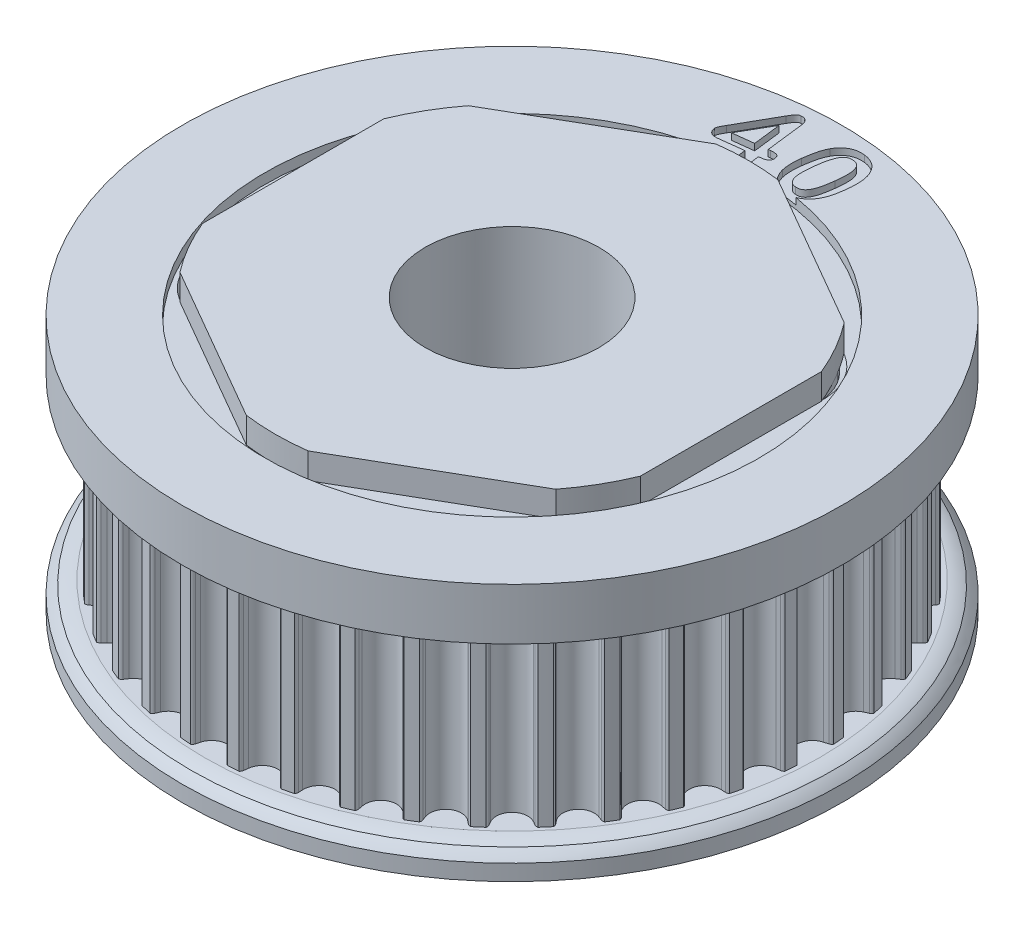
SolidWorks part; units mm, degrees
other "DetailItem2"
material "Markforged"
ref_plane "Front Plane" through (0, 0, 0) normal (0, 0, 1) x (1, 0, 0)
ref_plane "Top Plane" through (0, 0, 0) normal (0, 1, 0) x (1, 0, 0)
ref_plane "Right Plane" through (0, 0, 0) normal (1, 0, 0) x (0, 0, -1)
ref_axis "Centerline" through (0, 8.7312, 0) along (0, -1, 0)
sketch "Sketch1" plane through (0, 0, 0) normal (0, 1, 0) x (1, 0, 0)
  circle A0 centre (0, 0) radius 18.7176
  dimension "OuterDiameter" = 37.4352
extrude "ToothOD" add sketch "Sketch1" along normal mid plane 12.3825
sketch "Sketch2" plane through (0, 0, 0) normal (0, 1, 0) x (1, 0, 0)
  line L0 (0, 17.5492) -> (50000, 17.5492) construction
  line L1 (0, 18.7176) -> (50000, 18.7176) construction
  line L2 (0, 0) -> (0, 50000) construction
  arc A0 (-0.937, 18.2677) -> (0, 17.5492) centre (0, 18.5195) ccw
  arc A1 (-1.1278, 18.6836) -> (1.1278, 18.6836) centre (0, 0) cw
  circle A2 centre (0, 0) radius 18.7176 construction
  arc A3 (-0.937, 18.2677) -> (-1.0078, 18.5195) centre (-11.9754, 15.3012) ccw
  arc A4 (-1.0078, 18.5195) -> (-1.1278, 18.6836) centre (-1.2954, 18.4351) ccw
  circle A5 centre (0, 0) radius 18.7176 construction
  arc A6 (0.937, 18.2677) -> (1.0078, 18.5195) centre (11.9754, 15.3012) cw
  arc A7 (1.0078, 18.5195) -> (1.1278, 18.6836) centre (1.2954, 18.4351) cw
  arc A8 (0, 17.5492) -> (0.937, 18.2677) centre (0, 18.5195) ccw
  dimension "D1" = 1.9406
  dimension "D3" = 22.86
  dimension "D4" = 0.5994
  dimension "D2" = 1.1684
  dimension "D5" = 1.2954
extrude "ToothProfile" cut sketch "Sketch2" against normal through all both and the other way through all
pattern_circular "ToothPattern" count 40 over 360 about axis through (0, 6.1913, 0) along (0, -1, 0) of "ToothProfile"
sketch "Sketch4" plane through (0, 0, 0) normal (0, 0, 1) x (1, 0, 0)
  line L0 (0, -6.1913) -> (18.9716, -6.1913)
  line L1 (0, -7.9375) -> (20.32, -7.9375)
  line L2 (0, -7.9375) -> (0, -6.1913)
  line L3 (20.32, -7.9375) -> (20.32, -6.9532)
  line L4 (0, 0) -> (50000, 0) construction
  line L5 (20.32, 7.9375) -> (20.32, 6.9532)
  line L6 (0, 7.9375) -> (0, 6.1913)
  line L7 (0, 7.9375) -> (20.32, 7.9375)
  line L8 (0, 6.1913) -> (18.9716, 6.1913) construction
  line L9 (0, 6.1913) -> (0, 3.9688)
  line L10 (0, 3.9688) -> (18.9716, 3.9688)
  line L11 (18.9716, 3.9688) -> (20.32, 4.7473)
  line L12 (20.32, 4.7473) -> (20.32, 6.9532)
  line L13 (18.9716, 3.9688) -> (18.9716, 6.1913) construction
  arc A0 (18.9716, -6.1913) -> (19.812, -6.4452) centre (18.6641, -8.7261) cw
  arc A2 (19.812, -6.4452) -> (20.32, -6.9532) centre (17.815, -8.9503) cw
  arc A3 (19.812, 6.4452) -> (20.32, 6.9532) centre (17.815, 8.9503) ccw construction
  arc A4 (18.9716, 6.1913) -> (19.812, 6.4452) centre (18.6641, 8.7261) ccw construction
  dimension "D5" = 2.5534
  dimension "D6" = 3.2036
  dimension "FlangeID" = 18.9716
  dimension "D1" = 1.7463
  dimension "D2" = 0.9843
  dimension "D3" = 6.1913
  dimension "D4" = 15.875
  dimension "D7" = 0.762
  dimension "D8" = 0.508
  dimension "D10" = 0.508
  dimension "D9" = 20.32
  dimension "D11" = 10.16
  dimension "D12" = 30
revolve "Flange" add sketch "Sketch4" angle 360 about axis through (0, 8.7312, 0) along (0, -1, 0)
sketch "Sketch7" plane through (0, 0, 0) normal (0, -1, 0) x (1, 0, 0)
  circle A0 centre (0, 0) radius 5.3581
  dimension "D1" = 10.7163
extrude "Bore" cut sketch "Sketch7" against normal through all both and the other way through all
sketch "Sketch9" plane through (0, 7.9375, 0) normal (0, 1, 0) x (1, 0, 0)
  arc A0 (-10.7763, -10.7763) -> (10.7763, -10.7763) centre (0, 0) cw construction
  text T0 "40" font "Arial Rounded MT Bold" height 4.572
  point P3 (0, 15.24)
  dimension "D1" = 15.24
  dimension "D2" = 270
extrude "Large Tooth Count" cut sketch "Sketch9" against normal blind 0.4 and the other way through all
sketch "Sketch11" plane through (0, 7.9375, 0) normal (0, 1, 0) x (1, 0, 0)
  arc A0 (-4.8314, -4.8314) -> (4.8314, -4.8314) centre (0, 0) cw construction
  text T0 "<b>40</b>" font "Arial Rounded MT Bold" height 2.286
  point P6 (0, 6.8326)
  dimension "D4" = 6.8326
  dimension "D3" = 270
extrude "Small Tooth Count" [suppressed] cut sketch "Sketch11" against normal blind 0.4 and the other way through all
sketch "Sketch14" plane through (0, 0, 0) normal (0, 0, 1) x (1, 0, 0)
  line L0 (20.32, 7.9375) -> (-20.32, 7.9375) construction
  line L1 (0, 7.9375) -> (15.24, 7.9375)
  line L2 (0, 7.9375) -> (0, 7.3025)
  line L3 (0, 7.3025) -> (15.24, 7.3025)
  line L4 (15.24, 7.9375) -> (15.24, 7.3025)
  line L5 (0, 7.9375) -> (15.24, 7.3025) construction
  line L6 (0, 7.3025) -> (15.24, 7.9375) construction
  line L7 (-20.32, -7.9375) -> (20.32, -7.9375) construction
  line L8 (0, -7.9375) -> (15.24, -7.9375)
  line L9 (0, -7.9375) -> (0, -2.2225)
  line L10 (0, -2.2225) -> (15.24, -2.2225)
  line L11 (15.24, -7.9375) -> (15.24, -2.2225)
  line L12 (0, -7.9375) -> (15.24, -2.2225) construction
  line L13 (0, -2.2225) -> (15.24, -7.9375) construction
  line L14 (0, 0) -> (0, 50000) construction
  point P4 (7.62, 7.62)
  point P11 (7.62, -5.08)
  dimension "D1" = 9.525
  dimension "D2" = 15.24
  dimension "D3" = 10.16
revolve "Cut-Revolve1" cut sketch "Sketch14" angle 360 about L14
sketch "Sketch15" plane through (0, -7.9375, 0) normal (0, -1, 0) x (1, 0, 0)
  line L0 (0, 0) -> (0, 11.43) construction
  line L1 (-3.175, 0) -> (-3.175, 11.43)
  line L2 (3.175, 0) -> (3.175, 11.43)
  arc A0 (-3.175, 0) -> (3.175, 0) centre (0, 0) ccw
  arc A1 (3.175, 11.43) -> (-3.175, 11.43) centre (0, 11.43) ccw
  point P3 (0, 5.715)
  dimension "D1" = 3.175
  dimension "D2" = 11.43
extrude "Cut-Extrude1" cut sketch "Sketch15" against normal through all
pattern_circular "CirPattern1" count 6 over 360 about axis through (0, 7.9375, 0) along (0, -1, 0) of "Cut-Extrude1"
fillet "Fillet1" radius 3.175 6 edges at (-6.35, 2.54, 0) (-3.175, 2.54, -5.4993) (3.175, 2.54, -5.4993) (6.35, 2.54, 0) (-3.175, 2.54, 5.4993) (3.175, 2.54, 5.4993)
sketch "Sketch17" plane through (0, -2.2225, 0) normal (0, -1, 0) x (1, 0, 0)
  line L14 (3.175, 10.9985) -> (3.175, 11.43)
  line L16 (8.3112, 8.4646) -> (7.9375, 8.2489)
  line L18 (11.1125, 2.7496) -> (11.4862, 2.9654)
  line L20 (11.4862, -2.9654) -> (11.1125, -2.7496)
  line L22 (7.9375, -8.2489) -> (8.3112, -8.4646)
  line L24 (3.175, -11.43) -> (3.175, -10.9985)
  line L26 (-3.175, -10.9985) -> (-3.175, -11.43)
  line L28 (-8.3112, -8.4646) -> (-7.9375, -8.2489)
  line L30 (-11.1125, -2.7496) -> (-11.4862, -2.9654)
  line L32 (-11.4862, 2.9654) -> (-11.1125, 2.7496)
  line L34 (-7.9375, 8.2489) -> (-8.3112, 8.4646)
  line L37 (-3.175, 11.43) -> (-3.175, 10.9985)
  line L50 (3.175, 10.9985) -> (3.175, 11.43)
  line L51 (8.3112, 8.4646) -> (7.9375, 8.2489)
  line L52 (11.1125, 2.7496) -> (11.4862, 2.9654)
  line L53 (11.4862, -2.9654) -> (11.1125, -2.7496)
  line L54 (7.9375, -8.2489) -> (8.3112, -8.4646)
  line L55 (3.175, -11.43) -> (3.175, -10.9985)
  line L56 (-3.175, -10.9985) -> (-3.175, -11.43)
  line L57 (-8.3112, -8.4646) -> (-7.9375, -8.2489)
  line L58 (-11.1125, -2.7496) -> (-11.4862, -2.9654)
  line L59 (-11.4862, 2.9654) -> (-11.1125, 2.7496)
  line L60 (-7.9375, 8.2489) -> (-8.3112, 8.4646)
  line L61 (-3.175, 11.43) -> (-3.175, 10.9985)
  circle A1 centre (0, 0) radius 5.3581 construction
  circle A8 centre (0, 0) radius 5.3581
  arc A47 (3.175, 10.9985) -> (7.9375, 8.2489) centre (6.35, 10.9985) ccw
  arc A48 (11.4862, 2.9654) -> (8.3112, 8.4646) centre (9.8987, 5.715) ccw
  arc A49 (11.1125, 2.7496) -> (11.1125, -2.7496) centre (12.7, 0) ccw
  arc A50 (8.3112, -8.4646) -> (11.4862, -2.9654) centre (9.8987, -5.715) ccw
  arc A51 (7.9375, -8.2489) -> (3.175, -10.9985) centre (6.35, -10.9985) ccw
  arc A52 (-3.175, -11.43) -> (3.175, -11.43) centre (0, -11.43) ccw
  arc A53 (-3.175, -10.9985) -> (-7.9375, -8.2489) centre (-6.35, -10.9985) ccw
  arc A54 (-11.4862, -2.9654) -> (-8.3112, -8.4646) centre (-9.8987, -5.715) ccw
  arc A55 (-11.1125, -2.7496) -> (-11.1125, 2.7496) centre (-12.7, 0) ccw
  arc A56 (-8.3112, 8.4646) -> (-11.4862, 2.9654) centre (-9.8987, 5.715) ccw
  arc A57 (-7.9375, 8.2489) -> (-3.175, 10.9985) centre (-6.35, 10.9985) ccw
  arc A70 (3.175, 11.43) -> (-3.175, 11.43) centre (0, 11.43) ccw
  arc A71 (3.175, 10.9985) -> (7.9375, 8.2489) centre (6.35, 10.9985) ccw
  arc A72 (11.4862, 2.9654) -> (8.3112, 8.4646) centre (9.8987, 5.715) ccw
  arc A73 (11.1125, 2.7496) -> (11.1125, -2.7496) centre (12.7, 0) ccw
  arc A74 (8.3112, -8.4646) -> (11.4862, -2.9654) centre (9.8987, -5.715) ccw
  arc A75 (7.9375, -8.2489) -> (3.175, -10.9985) centre (6.35, -10.9985) ccw
  arc A76 (-3.175, -11.43) -> (3.175, -11.43) centre (0, -11.43) ccw
  arc A77 (-3.175, -10.9985) -> (-7.9375, -8.2489) centre (-6.35, -10.9985) ccw
  arc A78 (-11.4862, -2.9654) -> (-8.3112, -8.4646) centre (-9.8987, -5.715) ccw
  arc A79 (-11.1125, -2.7496) -> (-11.1125, 2.7496) centre (-12.7, 0) ccw
  arc A80 (-8.3112, 8.4646) -> (-11.4862, 2.9654) centre (-9.8987, 5.715) ccw
  arc A81 (-7.9375, 8.2489) -> (-3.175, 10.9985) centre (-6.35, 10.9985) ccw
  arc A82 (3.175, 11.43) -> (-3.175, 11.43) centre (0, 11.43) ccw
  dimension "D1" = 0
extrude "Boss-Extrude1" add sketch "Sketch17" against normal up to surface (9.525 mm away) separate body up to face at (0, 7.3025, 0)
sketch "Sketch21" plane through (0, -2.2225, 0) normal (0, -1, 0) x (1, 0, 0)
  circle A0 centre (0, 0) radius 7.9375
  dimension "D1" = 15.875
extrude "Cut-Extrude4" cut sketch "Sketch21" against normal blind 2.286
chamfer "Chamfer1" distance 2.54 angle 45 1 edges at (0, -7.9375, -15.24)
chamfer "Chamfer2" distance 0.635 angle 45 1 edges at (0, -2.2225, -15.24)
sketch "Sketch22" plane through (0, 7.3025, 0) normal (0, 1, 0) x (1, 0, 0)
  circle A0 centre (0, 0) radius 5.3581
  circle A1 centre (0, 0) radius 14.605
  arc A2 (8.3112, -8.4646) -> (11.4862, -2.9654) centre (9.8987, -5.715) ccw construction
  circle A3 centre (0, 0) radius 5.3581 construction
extrude "Boss-Extrude2" add sketch "Sketch22" along normal blind 1.5875 separate body
combine bodies "Combine1" operation type add bodies to combine 118 117
sketch "Sketch23" plane through (0, 7.3025, 0) normal (0, 1, 0) x (1, 0, 0)
  line L0 (7.9058, -8.3039) -> (8.2794, -8.5196)
  line L1 (11.5179, -2.9104) -> (11.1442, -2.6946)
  line L2 (11.1442, 2.6946) -> (11.5179, 2.9104)
  line L3 (8.2794, 8.5196) -> (7.9057, 8.3039)
  line L4 (3.2385, 10.9985) -> (3.2385, 11.43)
  line L5 (-3.2385, 11.43) -> (-3.2385, 10.9985)
  line L6 (-7.9058, 8.3039) -> (-8.2794, 8.5196)
  line L7 (-11.5179, 2.9104) -> (-11.1442, 2.6946)
  line L8 (-11.1442, -2.6946) -> (-11.5179, -2.9104)
  line L9 (-8.2794, -8.5196) -> (-7.9057, -8.3039)
  line L10 (-3.2385, -10.9985) -> (-3.2385, -11.43)
  line L11 (3.2385, -11.43) -> (3.2385, -10.9985)
  line L12 (7.9375, -8.2489) -> (8.3112, -8.4646)
  line L13 (3.175, -11.43) -> (3.175, -10.9985)
  line L14 (-3.175, -10.9985) -> (-3.175, -11.43)
  line L15 (-8.3112, -8.4646) -> (-7.9375, -8.2489)
  line L16 (-11.1125, -2.7496) -> (-11.4862, -2.9654)
  line L17 (-11.4862, 2.9654) -> (-11.1125, 2.7496)
  line L18 (-7.9375, 8.2489) -> (-8.3112, 8.4646)
  line L19 (-3.175, 11.43) -> (-3.175, 10.9985)
  line L20 (3.175, 10.9985) -> (3.175, 11.43)
  line L21 (8.3112, 8.4646) -> (7.9375, 8.2489)
  line L22 (11.1125, 2.7496) -> (11.4862, 2.9654)
  line L23 (11.4862, -2.9654) -> (11.1125, -2.7496)
  line L24 (7.9375, -8.2489) -> (8.3112, -8.4646)
  line L25 (3.175, -11.43) -> (3.175, -10.9985)
  line L26 (-3.175, -10.9985) -> (-3.175, -11.43)
  line L27 (-8.3112, -8.4646) -> (-7.9375, -8.2489)
  line L28 (-11.1125, -2.7496) -> (-11.4862, -2.9654)
  line L29 (-11.4862, 2.9654) -> (-11.1125, 2.7496)
  line L30 (-7.9375, 8.2489) -> (-8.3112, 8.4646)
  line L31 (-3.175, 11.43) -> (-3.175, 10.9985)
  line L32 (3.175, 10.9985) -> (3.175, 11.43)
  line L33 (8.3112, 8.4646) -> (7.9375, 8.2489)
  line L34 (11.1125, 2.7496) -> (11.4862, 2.9654)
  line L35 (11.4862, -2.9654) -> (11.1125, -2.7496)
  arc A0 (8.2794, -8.5196) -> (11.5179, -2.9104) centre (9.8987, -5.715) ccw
  arc A1 (11.1442, 2.6946) -> (11.1442, -2.6946) centre (12.7, 0) ccw
  arc A2 (11.5179, 2.9104) -> (8.2794, 8.5196) centre (9.8987, 5.715) ccw
  arc A3 (3.2385, 10.9985) -> (7.9057, 8.3039) centre (6.35, 10.9985) ccw
  arc A4 (3.2385, 11.43) -> (-3.2385, 11.43) centre (0, 11.43) ccw
  arc A5 (-7.9058, 8.3039) -> (-3.2385, 10.9985) centre (-6.35, 10.9985) ccw
  arc A6 (-8.2794, 8.5196) -> (-11.5179, 2.9104) centre (-9.8987, 5.715) ccw
  arc A7 (-11.1442, -2.6946) -> (-11.1442, 2.6946) centre (-12.7, 0) ccw
  arc A8 (-11.5179, -2.9104) -> (-8.2794, -8.5196) centre (-9.8987, -5.715) ccw
  arc A9 (-3.2385, -10.9985) -> (-7.9057, -8.3039) centre (-6.35, -10.9985) ccw
  arc A10 (-3.2385, -11.43) -> (3.2385, -11.43) centre (0, -11.43) ccw
  arc A11 (7.9058, -8.3039) -> (3.2385, -10.9985) centre (6.35, -10.9985) ccw
  arc A12 (7.9375, -8.2489) -> (3.175, -10.9985) centre (6.35, -10.9985) ccw
  arc A13 (-3.175, -11.43) -> (3.175, -11.43) centre (0, -11.43) ccw
  arc A14 (-3.175, -10.9985) -> (-7.9375, -8.2489) centre (-6.35, -10.9985) ccw
  arc A15 (-11.4862, -2.9654) -> (-8.3112, -8.4646) centre (-9.8987, -5.715) ccw
  arc A16 (-11.1125, -2.7496) -> (-11.1125, 2.7496) centre (-12.7, 0) ccw
  arc A17 (-8.3112, 8.4646) -> (-11.4862, 2.9654) centre (-9.8987, 5.715) ccw
  arc A18 (-7.9375, 8.2489) -> (-3.175, 10.9985) centre (-6.35, 10.9985) ccw
  arc A19 (3.175, 11.43) -> (-3.175, 11.43) centre (0, 11.43) ccw
  arc A20 (3.175, 10.9985) -> (7.9375, 8.2489) centre (6.35, 10.9985) ccw
  arc A21 (11.4862, 2.9654) -> (8.3112, 8.4646) centre (9.8987, 5.715) ccw
  arc A22 (11.1125, 2.7496) -> (11.1125, -2.7496) centre (12.7, 0) ccw
  arc A23 (8.3112, -8.4646) -> (11.4862, -2.9654) centre (9.8987, -5.715) ccw
  arc A24 (7.9375, -8.2489) -> (3.175, -10.9985) centre (6.35, -10.9985) ccw
  arc A25 (-3.175, -11.43) -> (3.175, -11.43) centre (0, -11.43) ccw
  arc A26 (-3.175, -10.9985) -> (-7.9375, -8.2489) centre (-6.35, -10.9985) ccw
  arc A27 (-11.4862, -2.9654) -> (-8.3112, -8.4646) centre (-9.8987, -5.715) ccw
  arc A28 (-11.1125, -2.7496) -> (-11.1125, 2.7496) centre (-12.7, 0) ccw
  arc A29 (-8.3112, 8.4646) -> (-11.4862, 2.9654) centre (-9.8987, 5.715) ccw
  arc A30 (-7.9375, 8.2489) -> (-3.175, 10.9985) centre (-6.35, 10.9985) ccw
  arc A31 (3.175, 11.43) -> (-3.175, 11.43) centre (0, 11.43) ccw
  arc A32 (3.175, 10.9985) -> (7.9375, 8.2489) centre (6.35, 10.9985) ccw
  arc A33 (11.4862, 2.9654) -> (8.3112, 8.4646) centre (9.8987, 5.715) ccw
  arc A34 (11.1125, 2.7496) -> (11.1125, -2.7496) centre (12.7, 0) ccw
  arc A35 (8.3112, -8.4646) -> (11.4862, -2.9654) centre (9.8987, -5.715) ccw
  dimension "D1" = 0
  dimension "D2" = 0.0635
extrude "Cut-Extrude5" cut sketch "Sketch23" against normal through all
chamfer "Chamfer3" distance 0.3175 angle 45 54 edges at (-4.7942, 7.3025, 8.3039) (-3.2385, 7.3025, 11.2143) (-8.0926, 7.3025, 8.4118) (0, 7.3025, 14.6685) (-12.7033, 7.3025, 7.3342) (3.2385, 7.3025, 11.2143) (-11.3311, 7.3025, 2.8025) (4.7943, 7.3025, 8.3039) (-9.5885, 7.3025, 0) (8.0926, 7.3025, 8.4118) (-11.3311, 7.3025, -2.8025) (12.7033, 7.3025, 7.3343) (-12.7033, 7.3025, -7.3343) (11.3311, 7.3025, 2.8025) (-8.0926, 7.3025, -8.4118) (9.5885, 7.3025, 0) (-4.7943, 7.3025, -8.3039) (11.3311, 7.3025, -2.8025) (-3.2385, 7.3025, -11.2143) (12.7033, 7.3025, -7.3342) (0, 7.3025, -14.6685) (8.0926, 7.3025, -8.4118) (3.2385, 7.3025, -11.2143) (4.7942, 7.3025, -8.3039) (-10.3811, -2.2225, 8.9174) (-2.5321, -2.2225, 13.449) (-8.0926, -2.2225, 8.4118) (-3.2385, -2.2225, 11.2143) (-4.7942, -2.2225, 8.3039) (2.5321, -2.2225, 13.449) (10.3811, -2.2225, 8.9174) (3.2385, -2.2225, 11.2143) (8.0926, -2.2225, 8.4118) (4.7943, -2.2225, 8.3039) (12.9132, -2.2225, 4.5316) (12.9132, -2.2225, -4.5316) (11.3311, -2.2225, 2.8025) (11.3311, -2.2225, -2.8025) (9.5885, -2.2225, 0) (10.3811, -2.2225, -8.9174) (2.5321, -2.2225, -13.449) (8.0926, -2.2225, -8.4118) (3.2385, -2.2225, -11.2143) (4.7942, -2.2225, -8.3039) (-2.5321, -2.2225, -13.449) (-10.3811, -2.2225, -8.9174) (-3.2385, -2.2225, -11.2143) (-8.0926, -2.2225, -8.4118) (-4.7943, -2.2225, -8.3039) (-12.9132, -2.2225, -4.5316) (-12.9132, -2.2225, 4.5316) (-11.3311, -2.2225, -2.8025) (-11.3311, -2.2225, 2.8025) (-9.5885, -2.2225, 0)
sketch "Sketch24" plane through (0, 8.89, 0) normal (0, 1, 0) x (1, 0, 0)
  line L1 (0, 15.5812) -> (-13.4938, 7.7906)
  line L2 (-13.4938, 7.7906) -> (-13.4938, -7.7906)
  line L3 (-13.4938, -7.7906) -> (0, -15.5812)
  line L4 (0, -15.5812) -> (13.4937, -7.7906)
  line L5 (13.4937, -7.7906) -> (13.4938, 7.7906)
  line L6 (13.4938, 7.7906) -> (0, 15.5812)
  circle A0 centre (0, 0) radius 13.4938 construction
  circle A1 centre (0, 0) radius 20.32
  circle A3 centre (0, 0) radius 20.32 construction
  dimension "D1" = 26.9875
extrude "Cut-Extrude6" cut sketch "Sketch24" against normal through all
delete or keep bodies "Body-Delete/Keep 1" [suppressed] bodies 119
delete or keep bodies "Body-Delete/Keep 2" [suppressed] type keep bodies bodies 120
delete or keep bodies "Body-Delete/Keep 3" [suppressed] type keep bodies bodies 118
equation "\"OuterDiameter@Sketch1\"= \"OD\""
equation "\"Teeth\"= \"No_Teeth\""
equation "\"PD\"= \"No_Teeth\" * 3mm / pi"
equation "\"OD\"= \"PD\" - .030"
equation "\"ToothCount@ToothPattern\" = \"Teeth\""
equation "\"Angle\"= 360 / \"Teeth\""
equation "\"AngleSpacing@ToothPattern\" = \"Angle\""
equation "\"FlangeID@Sketch4\"=\"OD\"/2+.01"
equation "\"D3@Sketch4\"=\"Tooth_Face_Length\"/2"
equation "\"Bearing_Feature\"= \"Bearing_Boss\""
equation "\"TopBearingBoss\" = IIF ( \"Bearing_Feature\" > 0 , \"unsuppressed\" , \"suppressed\" )"
equation "\"HexBore\"= \"Hex_Bore\" + \"Print_Tolerance\""
equation "\"Large Tooth Count\" = iif ( \"No_Teeth\" < \"TextTooth\" , \"suppressed\" , \"unsuppressed\" )"
equation "\"Small Tooth Count\"= iif ( \"No_Teeth\" < \"TextTooth\" , \"unsuppressed\" , \"suppressed\" )"
equation "\"BottomBearingBoss\" = iif ( \"Bearing_Feature\" > 1 , \"unsuppressed\" , \"suppressed\" )"
equation "\"ToothFaceLength@ToothOD\" = \"Tooth_Face_Length\""
equation "\"D4@Sketch4\" = \"Width_No_BearingBoss\""
equation "\"TextTooth\"= iif ( \"Hex_Bore\" <= .380 , 23 , iif ( \"Hex_Bore\" <= .505 , 25 , 16 ) )"
equation "\"D4@Sketch11\"=\"HexBore\"/2+.08"
